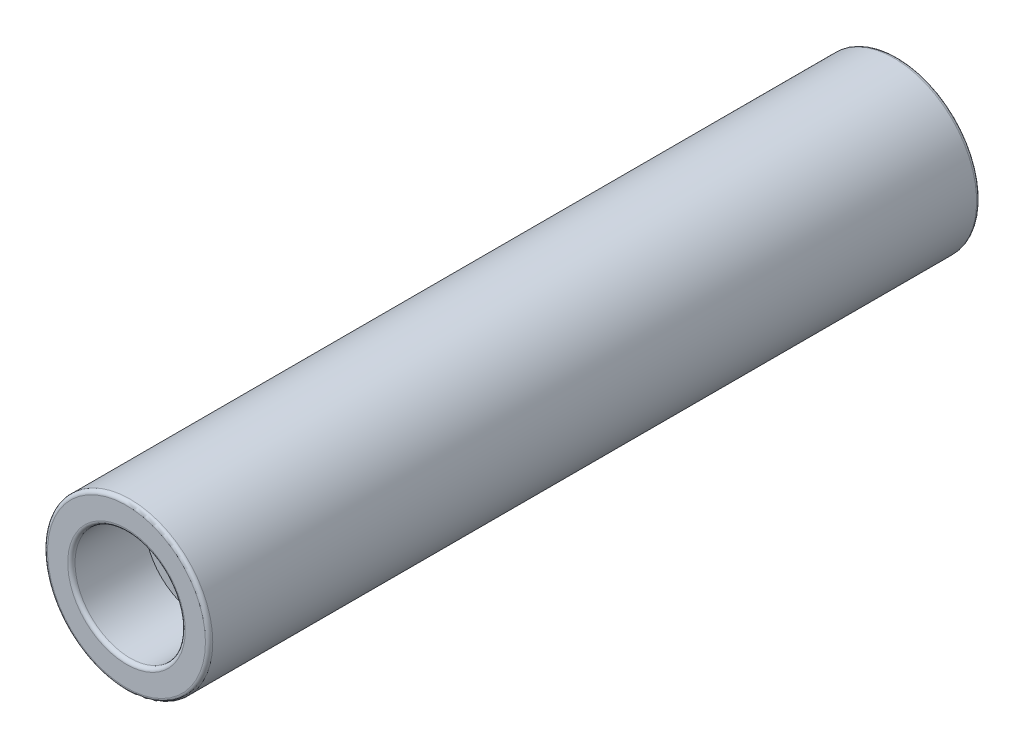
SolidWorks part; units mm, degrees
ref_plane "Front Plane" through (0, 0, 0) normal (0, 0, 1) x (1, 0, 0)
ref_plane "Top Plane" through (0, 0, 0) normal (0, 1, 0) x (1, 0, 0)
ref_plane "Right Plane" through (0, 0, 0) normal (1, 0, 0) x (0, 0, -1)
sketch "Sketch1" plane through (0, 0, 0) normal (0, 0, 1) x (1, 0, 0)
  circle A0 centre (0, 0) radius 4.5
  dimension "D1" = 9
extrude "Extrude-Thin1" add sketch "Sketch1" along normal blind 12 thin contours A0 thin type one direction reverse wall 3
sketch "Sketch11" plane through (0, 0, 12) normal (0, 0, 1) x (1, 0, 0)
  circle A0 centre (0, 0) radius 1.5
  dimension "D1" = 3
extrude "Extrude-Thin3" add sketch "Sketch11" along normal blind 5 thin thin type one direction wall 3
sketch "Sketch12" plane through (0, 0, 17) normal (0, 0, 1) x (1, 0, 0)
  circle A0 centre (0, 0) radius 3
  dimension "D1" = 6
extrude "Extrude-Thin4" add sketch "Sketch12" along normal blind 4 thin thin type one direction wall 1.5
thread "Thread1" pitch 0.5 method extrude profile "Thread Profile1" start angle 0, offset 0, length 5, pitch 0.5, diameter 3
ref_plane "Plane6" through (-1.5, 0, 17) normal (0, -1, 0) x (-1, 0, 0)
sketch "Thread Profile1" plane through (-1.5, 0, 17) normal (0, -1, 0) x (-1, 0, 0)
  line L0 (0, 0) -> (0, 0.5) construction
  line L11 (0, 0) -> (0, 0.4375)
  line L12 (0, 0.4375) -> (-0.2706, 0.2812)
  line L13 (-0.2706, 0.2812) -> (-0.2706, 0.1562)
  line L15 (-0.2706, 0.1562) -> (0, 0)
  line L17 (-0.2706, 0.2187) -> (0, 0.2187) construction
  point P2 (0, 0)
  dimension "Pitch" = 0.5
  dimension "Profile_Angle" = 60
  dimension "Profile_Land" = 0.125
  dimension "Profile_Height" = 0.2706
mirror "Mirror2" about plane through (0, 0, 0) normal (0, 0, 1) of "Extrude-Thin4", "Extrude-Thin3", "Thread1", "Extrude-Thin1"
fillet "Fillet2" radius 0.2 4 edges at (4.5, 0, -21) (3, 0, -21) (4.5, 0, 21) (3, 0, 21)
